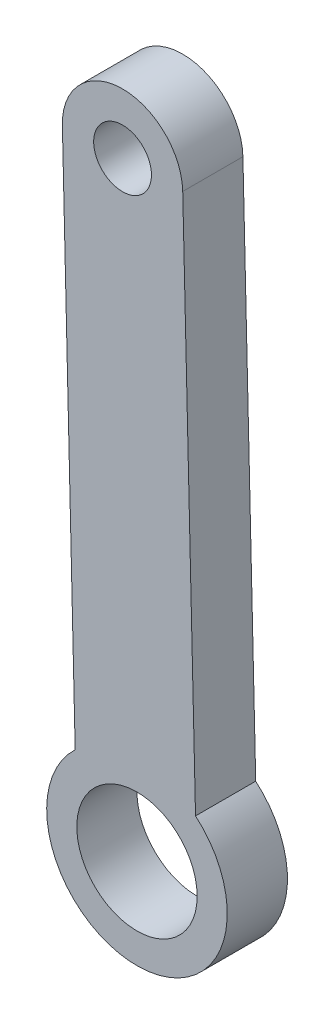
SolidWorks part; units mm, degrees
ref_plane "Front Plane" through (0, 0, 0) normal (0, 0, 1) x (1, 0, 0)
ref_plane "Top Plane" through (0, 0, 0) normal (0, 1, 0) x (1, 0, 0)
ref_plane "Right Plane" through (0, 0, 0) normal (1, 0, 0) x (0, 0, -1)
sketch "Sketch1" plane through (0, 0, 0) normal (0, 0, 1) x (0.9997, 0.0239, 0)
  line L0 (10.01, -0.02) -> (5.01, -0.02) construction
  line L1 (10.01, 49.98) -> (0.01, 49.98) construction
  line L2 (10.01, 49.98) -> (10.01, -0.02)
  line L3 (10.01, -0.02) -> (0.01, -0.02) construction
  line L4 (0.01, 49.98) -> (0.01, -0.02)
  line L6 (10.01, 24.98) -> (0.01, 24.98) construction
  circle A1 centre (5.01, 49.98) radius 2.4
  arc A2 (0.01, -0.02) -> (10.01, -0.02) centre (5.01, -0.02) ccw
  arc A3 (10.01, 49.98) -> (0.01, 49.98) centre (5.01, 49.98) ccw
  circle A4 centre (5.01, -0.02) radius 7.5
  circle A5 centre (5.01, -0.02) radius 5
  dimension "D1" = 4.8
  dimension "D4" = 15
  dimension "D6" = 10
  dimension "D2" = 50
  dimension "D3" = 10
  dimension "D5" = 50
extrude "Boss-Extrude1" add sketch "Sketch1" along normal blind 5 contours L6 L2 L1 L4 A1 | L2 L6 L4 L3 A5 L0 | A4 | A5 region at (4.2996, 29.7314, 0) region at (4.8833, 5.3544, 0)
move or copy body "Body-Move/Copy1" [suppressed] bodies to move or copy 101
